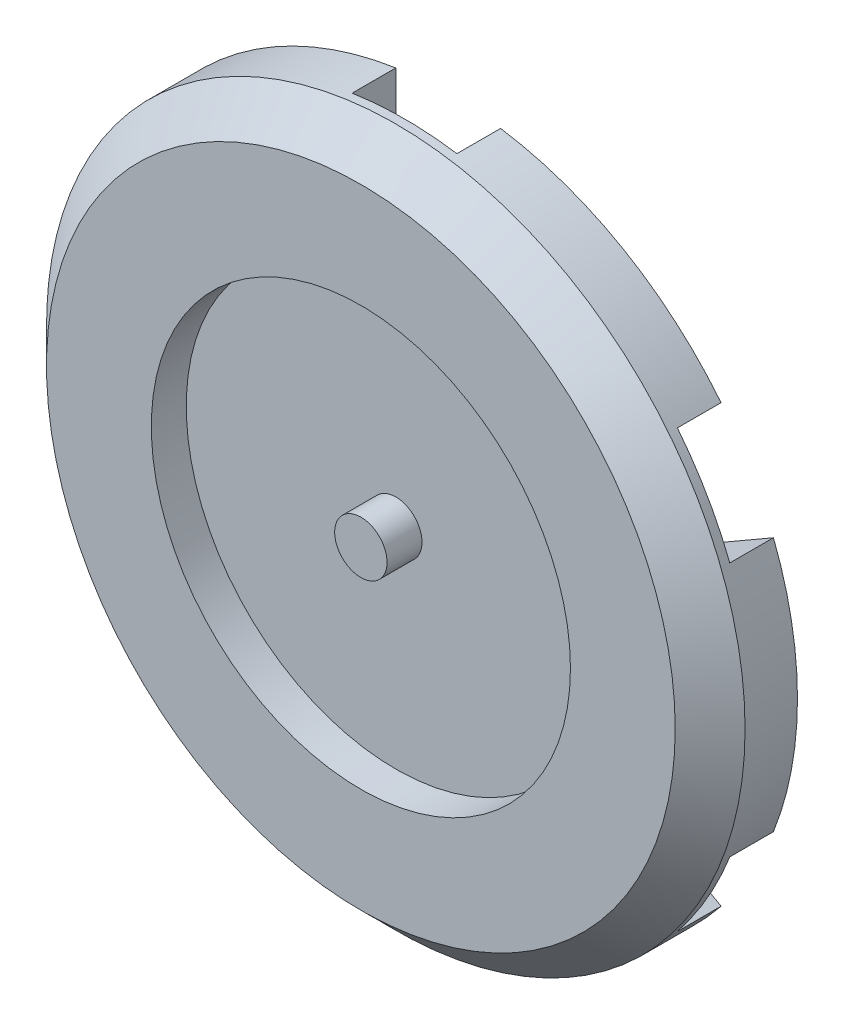
SolidWorks part; units mm, degrees
ref_plane "Front Plane" through (0, 0, 0) normal (1, 0, 0) x (0, 1, 0)
ref_plane "Top Plane" through (0, 0, 0) normal (0, 0, 1) x (0, 1, 0)
ref_plane "Right Plane" through (0, 0, 0) normal (0, 1, 0) x (-1, 0, 0)
sketch "Sketch1" plane through (0, 0, 0) normal (0, 0, 1) x (0, 1, 0)
  circle A0 centre (0, 0) radius 60
  circle A1 centre (0, 0) radius 100
  dimension "D1" = 120
  dimension "D2" = 200
extrude "Boss-Extrude1" add sketch "Sketch1" along normal blind 25 contours A0 | A1 A0 region at (0, 0, 0) region at (0, -97.1716, 0)
extrude "Cut-Extrude1" cut sketch "Sketch1<3>" against normal blind 10 from surface contours A0 region at (0, 0, 0) starting at face at (100, 0, 25)
sketch "Sketch1<3>" plane through (0, 0, 0) normal (0, 0, 1) x (0, 1, 0) same geometry as "Sketch1"
chamfer "Chamfer1" distance 10 angle 45 1 edges at (100, 0, 25)
sketch "Sketch3" plane through (0, 0, 0) normal (0, 0, -1) x (1, 0, 0)
  line L0 (0, 0) -> (0, 100) construction
  line L3 (-15, 98.8686) -> (-15, 68.8686)
  line L4 (-15, 68.8686) -> (15, 68.8686)
  line L5 (15, 98.8686) -> (15, 68.8686)
  circle A0 centre (0, 0) radius 100 construction
  arc A1 (15, 98.8686) -> (-15, 98.8686) centre (0, 0) ccw
  point P10 (0, 68.8686)
  dimension "D1" = 30
  dimension "D2" = 30
extrude "Cut-Extrude2" cut sketch "Sketch3" against normal blind 12.5
pattern_circular "CirPattern1" count 6 over 360 about axis through (0, 0, 0) along (0, 0, 1) of "Cut-Extrude2"
sketch "Sketch4" plane through (0, 0, 15) normal (0, 0, 1) x (1, 0, 0)
  circle A0 centre (0, 0) radius 7.5
  dimension "D1" = 15
extrude "Boss-Extrude2" add sketch "Sketch4" along normal blind 10
